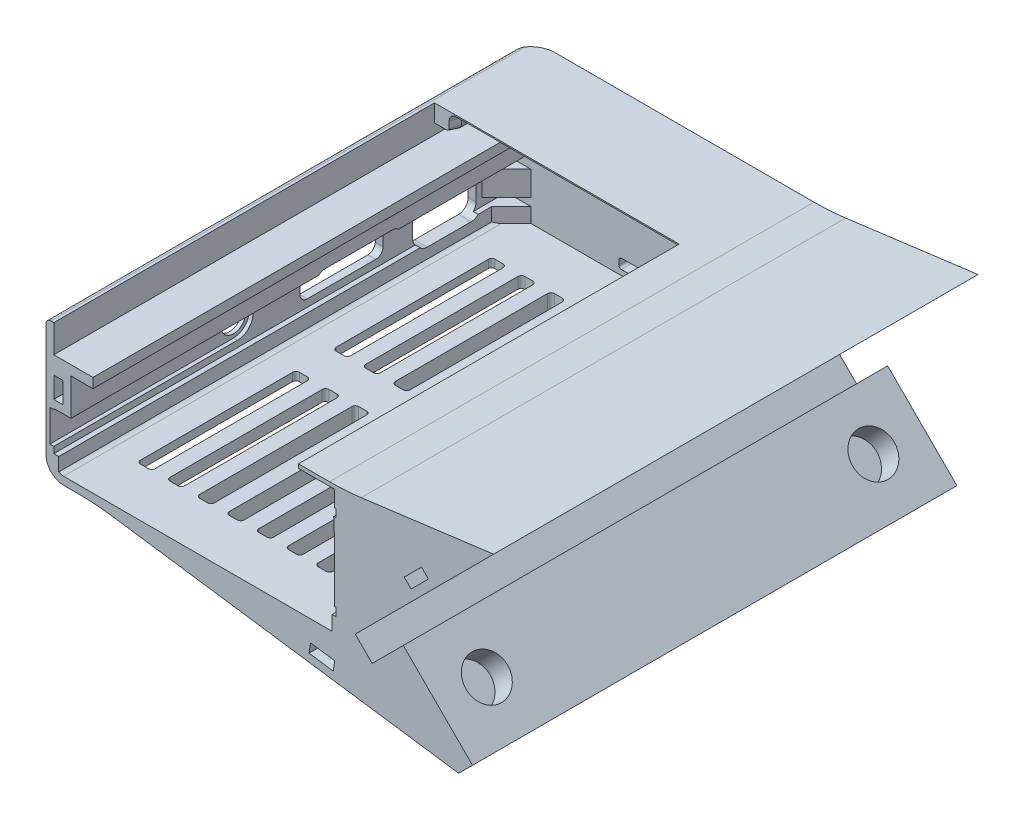
SolidWorks part; units mm, degrees
ref_plane "Front Plane" through (0, 0, 0) normal (0, 0, 1) x (1, 0, 0)
ref_plane "Top Plane" through (0, 0, 0) normal (0, 1, 0) x (1, 0, 0)
ref_plane "Right Plane" through (0, 0, 0) normal (1, 0, 0) x (0, 0, -1)
sketch "Sketch1" plane through (0, 0, 0) normal (0, 0, 1) x (1, 0, 0)
  line L0 (1.6, 5.9) -> (1.6, 3.6) construction
  line L1 (3.6, 0) -> (61.2, 0)
  line L2 (0, 3.6) -> (0, 26.8)
  line L3 (49.6, 27.8) -> (61.2, 27.8)
  line L4 (61.2, 0) -> (61.2, 27.8)
  line L5 (3.6, 1.6) -> (57, 1.6) construction
  line L6 (1.6, 5.9) -> (0.8, 5.9) construction
  line L7 (0.8, 5.9) -> (0.8, 12.4) construction
  line L8 (0.8, 12.4) -> (1.6, 12.4) construction
  line L9 (1.6, 12.4) -> (1.6, 22.1) construction
  line L10 (1.6, 5.9) -> (1.6, 12.4) construction
  line L11 (1, 27.8) -> (1.6, 27.8)
  line L12 (59, 3.6) -> (59, 22.1) construction
  line L13 (59, 4.6) -> (59.3, 4.6) construction
  line L14 (59.3, 4.6) -> (59.3, 6.1) construction
  line L15 (59.3, 6.1) -> (59, 6.1) construction
  line L16 (59, 22.1) -> (59.3, 22.1) construction
  line L17 (59.3, 22.1) -> (59.3, 23.6) construction
  line L18 (59.3, 23.6) -> (59, 23.6) construction
  line L19 (59, 23.6) -> (59, 27.2) construction
  line L20 (1.6, 22.1) -> (5.6, 22.1) construction
  line L21 (5.6, 22.1) -> (5.6, 23.6) construction
  line L22 (5.6, 23.6) -> (1.6, 23.6) construction
  line L23 (1.6, 23.6) -> (1.6, 27.8) construction
  line L24 (59, 27.2) -> (49.6, 27.2) construction
  line L25 (49.6, 27.2) -> (49.6, 27.8) construction
  line L26 (49.6, 27.8) -> (1.6, 27.8)
  arc A0 (3.6, 0) -> (0, 3.6) centre (3.6, 3.6) cw
  arc A1 (0, 26.8) -> (1, 27.8) centre (1, 26.8) cw
  arc A2 (1.6, 3.6) -> (3.6, 1.6) centre (3.6, 3.6) ccw construction
  arc A3 (57, 1.6) -> (59, 3.6) centre (57, 3.6) ccw construction
  point P7 (0, 0)
  dimension "D2" = 0.8
  dimension "D3" = 2
  dimension "D8" = 2
  dimension "D18" = 1
  dimension "D1" = 61.2
  dimension "D4" = 5.9
  dimension "D5" = 1.6
  dimension "D6" = 6.5
  dimension "D7" = 2.2
  dimension "D9" = 4.6
  dimension "D10" = 6.1
  dimension "D11" = 0.3
  dimension "D12" = 16
  dimension "D13" = 4
  dimension "D14" = 1.5
  dimension "D15" = 4.2
  dimension "D16" = 0.6
  dimension "D17" = 48
extrude "Boss-Extrude1" add sketch "Sketch1" along normal blind 94
sketch "Sketch2" plane through (0, 0, 94) normal (0, 0, 1) x (1, 0, 0)
  line L0 (51.6, 27.8) -> (51.6, 27)
  line L1 (59.3, 4.6) -> (59, 4.6)
  line L2 (51.6, 27) -> (59, 27)
  line L3 (1.6, 27.8) -> (1.6, 22.1)
  line L4 (1.6, 27.8) -> (1, 27.8) construction
  line L5 (61.2, 0) -> (61.2, 27.8)
  line L6 (61.2, 27.8) -> (1, 27.8)
  line L7 (0, 26.8) -> (0, 3.6)
  line L8 (3.6, 0) -> (61.2, 0)
  line L9 (61.2, 0) -> (61.2, 27.8) construction
  line L10 (61.2, 27.8) -> (51.6, 27.8) construction
  line L11 (0, 26.8) -> (0, 3.6) construction
  line L12 (3.6, 0) -> (61.2, 0) construction
  line L13 (1.6, 22.1) -> (9.6, 22.1)
  line L14 (9.6, 22.1) -> (9.6, 20.1)
  line L15 (9.6, 20.1) -> (5.1, 20.1)
  line L16 (59, 1.6) -> (3.6, 1.6)
  line L17 (1.6, 12.6) -> (1.6, 3.6)
  line L18 (1.6, 12.6) -> (5.1, 12.6)
  line L19 (5.1, 12.6) -> (5.1, 20.1)
  line L20 (59, 27) -> (59, 23.7)
  line L21 (59, 23.7) -> (59.3, 23.7)
  line L22 (59.3, 23.7) -> (59.3, 22.1)
  line L23 (59.3, 22.1) -> (59, 22.1)
  line L24 (59, 6.2) -> (59.3, 6.2)
  line L25 (59.3, 6.2) -> (59.3, 4.6)
  line L26 (59, 4.6) -> (59, 1.6)
  line L27 (59, 22.1) -> (59, 6.2)
  line L28 (1.6, 27.8) -> (51.6, 27.8)
  line L29 (51.6, 27.8) -> (51.599, 27.8897)
  arc A0 (1.6, 3.6) -> (3.6, 1.6) centre (3.6, 3.6) ccw
  arc A2 (1, 27.8) -> (0, 26.8) centre (1, 26.8) ccw
  arc A3 (0, 3.6) -> (3.6, 0) centre (3.6, 3.6) ccw
  arc A4 (1, 27.8) -> (0, 26.8) centre (1, 26.8) ccw construction
  arc A5 (0, 3.6) -> (3.6, 0) centre (3.6, 3.6) ccw construction
  line M8 (61.2, 27.8) -> (1, 27.8)
  dimension "D7" = 2
  dimension "D2" = 50
  dimension "D3" = 1.6
  dimension "D4" = 5.7
  dimension "D5" = 8
  dimension "D6" = 1.6
  dimension "D8" = 11
  dimension "D9" = 2
  dimension "D10" = 5.1
  dimension "D11" = 2.2
  dimension "D12" = 0.8
  dimension "D13" = 3.3
  dimension "D14" = 0.3
  dimension "D15" = 1.6
  dimension "D16" = 1.6
  dimension "D17" = 3
  dimension "D1" = 0
extrude "Cut-Extrude1" cut sketch "Sketch2" against normal offset from surface (92.5 mm away) 1.5 contours L17 A0 L16 L26 L1 L25 L24 L27 L23 L22 L21 L20 L2 L0 L3 L13 L14 L15 L19 L18 M8 region at (30.9914, 14.5554, 94) up to face at (21.0079, 14.2436, 0)
chamfer "Chamfer1" distance 5 angle 45 1 edges at (59, 3.1, 1.5)
sketch "Sketch3" plane through (0, 0, 1.5) normal (0, 0, 1) x (1, 0, 0)
  line L0 (1.6, 27.8) -> (1.6, 22.1) construction
  line L1 (51.6, 27.8) -> (1.6, 27.8)
  line L2 (51.6, 27.8) -> (51.6, 27)
  line L3 (51.6, 27) -> (6.1, 27)
  line L4 (1.6, 27.8) -> (1.6, 23.7)
  line L5 (51.6, 27) -> (59, 27) construction
  line L6 (5.1, 26) -> (5.1, 24.7)
  line L7 (4.1, 23.7) -> (1.6, 23.7)
  line L8 (59, 23.7) -> (59.3, 23.7) construction
  line L9 (5.1, 12.6) -> (5.1, 20.1) construction
  arc A0 (5.1, 26) -> (6.1, 27) centre (6.1, 26) cw
  arc A1 (5.1, 24.7) -> (4.1, 23.7) centre (4.1, 24.7) cw
  dimension "D1" = 1
extrude "Boss-Extrude2" add sketch "Sketch3" along normal blind 14.7
sketch "Sketch4" plane through (0, 4.6, 0) normal (0, 1, 0) x (1, 0, 0)
  line L0 (1.6, -1.5) -> (6.6, -1.5)
  line L1 (54, -1.5) -> (3.6, -1.5) construction
  line L2 (6.6, -1.5) -> (1.6, -6.5)
  line L3 (1.6, -1.5) -> (1.6, -94) construction
  line L4 (1.6, -6.5) -> (1.6, -1.5)
  dimension "D1" = 45
extrude "Boss-Extrude3" add sketch "Sketch4" against normal up to next
sketch "Sketch5" plane through (0, 6.2, 0) normal (0, -1, 0) x (1, 0, 0)
  line L0 (54, 1.5) -> (59, 6.5)
  line L1 (59, 6.5) -> (59, 1.5)
  line L2 (59, 1.5) -> (59, 94) construction
  line L3 (59, 1.5) -> (59.3, 1.5) construction
  line L4 (59, 1.5) -> (54, 1.5)
  line L5 (1.6, 1.5) -> (6.6, 1.5)
  line L6 (6.6, 1.5) -> (1.6, 6.5)
  line L7 (1.6, 6.5) -> (1.6, 1.5)
extrude "Boss-Extrude4" add sketch "Sketch5" against normal blind 5
sketch "Sketch18" plane through (0, 0, 94) normal (0, 0, 1) x (1, 0, 0)
  line L0 (59, 1.6) -> (54, 1.6) construction
  line L1 (59, 4.6) -> (58.5, 4.6)
  line L2 (59, 4.6) -> (59, 1.6)
  line L3 (59, 1.6) -> (58.5, 1.6)
  line L4 (58.5, 4.6) -> (58.5, 1.6)
  line L5 (59, 1.6) -> (3.6, 1.6) construction
  line L6 (1.6, 4.6) -> (2.6, 4.6)
  line L7 (1.6, 4.6) -> (1.6, 1.6)
  line L8 (1.6, 1.6) -> (2.6, 1.6)
  line L9 (2.6, 4.6) -> (2.6, 1.6)
  line L10 (59, 22.1) -> (58.8, 22.1)
  line L11 (58.8, 22.1) -> (59, 17.1)
  line L12 (59, 22.1) -> (59, 11.2) construction
  line L13 (59, 17.1) -> (59, 22.1)
  dimension "D1" = 1
  dimension "D2" = 0.5
  dimension "D3" = 0.2
  dimension "D4" = 5
sketch "Sketch6" plane through (0, 0, 0) normal (-1, 0, 0) x (0, 0, 1)
  line L0 (0, 26.8) -> (0, 3.6) construction
  line L1 (9.7, 12) -> (18.7, 12)
  line L2 (7.7, 10) -> (7.7, 6)
  line L3 (9.7, 4) -> (18.7, 4)
  line L4 (20.7, 10) -> (20.7, 6)
  line L5 (28.2, 13.1) -> (42.2, 13.1)
  line L6 (26.7, 11.6) -> (26.7, 7.6)
  line L7 (28.2, 6.1) -> (42.2, 6.1)
  line L8 (43.7, 11.6) -> (43.7, 7.6)
  line L9 (94, 0) -> (0, 0) construction
  arc A0 (7.7, 6) -> (9.7, 4) centre (9.7, 6) ccw
  arc A1 (18.7, 4) -> (20.7, 6) centre (18.7, 6) ccw
  arc A2 (18.7, 12) -> (20.7, 10) centre (18.7, 10) cw
  arc A3 (9.7, 12) -> (7.7, 10) centre (9.7, 10) ccw
  arc A4 (26.7, 7.6) -> (28.2, 6.1) centre (28.2, 7.6) ccw
  arc A5 (42.2, 6.1) -> (43.7, 7.6) centre (42.2, 7.6) ccw
  arc A6 (42.2, 13.1) -> (43.7, 11.6) centre (42.2, 11.6) cw
  arc A7 (28.2, 13.1) -> (26.7, 11.6) centre (28.2, 11.6) ccw
  circle A8 centre (56.5, 9.15) radius 2.5
  point P12 (7.7, 4)
  point P15 (20.7, 4)
  point P20 (7.7, 12)
  point P25 (26.7, 6.1)
  point P30 (43.7, 13.1)
  point P33 (26.7, 13.1)
  dimension "D4" = 2
  dimension "D10" = 1.5
  dimension "D11" = 5
  dimension "D12" = 9.15
  dimension "D13" = 48.8
  dimension "D1" = 7.7
  dimension "D2" = 13
  dimension "D3" = 8
  dimension "D5" = 4
  dimension "D6" = 19
  dimension "D7" = 2.1
  dimension "D8" = 7
  dimension "D9" = 17
extrude "Boss-Extrude9" add sketch "Sketch18" against normal up to next
extrude "Cut-Extrude2" cut sketch "Sketch6" against normal up to next
sketch "Sketch7" plane through (1.6, 0, 0) normal (1, 0, 0) x (0, 0, -1)
  line L0 (-56.5, 5.9) -> (-94, 5.9)
  line L1 (-94, 12.6) -> (-94, 4.6) construction
  line L2 (-94, 5.9) -> (-94, 12.4)
  line L3 (-94, 12.4) -> (-56.5, 12.4)
  line L4 (-4.5, 1.6) -> (-94, 1.6) construction
  arc A0 (-56.5, 5.9) -> (-56.5, 12.4) centre (-56.5, 9.15) ccw
  dimension "D1" = 4.3
extrude "Cut-Extrude3" cut sketch "Sketch7" against normal blind 0.8
sketch "Sketch8" plane through (0, 0, 1.5) normal (0, 0, 1) x (1, 0, 0)
  line L0 (59, 17.1) -> (59, 6.2) construction
  line L1 (25.1, 4.7) -> (37.9, 4.7)
  line L2 (24.6, 4.2) -> (24.6, 3.2)
  line L3 (25.1, 2.7) -> (37.9, 2.7)
  line L4 (38.4, 4.2) -> (38.4, 3.2)
  line L5 (58.5, 1.6) -> (3.6, 1.6) construction
  arc A0 (37.9, 4.7) -> (38.4, 4.2) centre (37.9, 4.2) cw
  arc A1 (37.9, 2.7) -> (38.4, 3.2) centre (37.9, 3.2) ccw
  arc A2 (24.6, 3.2) -> (25.1, 2.7) centre (25.1, 3.2) ccw
  arc A3 (25.1, 4.7) -> (24.6, 4.2) centre (25.1, 4.2) ccw
  point P10 (38.4, 4.7)
  point P15 (24.6, 2.7)
  point P18 (24.6, 4.7)
  dimension "D5" = 0.5
  dimension "D1" = 13.8
  dimension "D2" = 20.6
  dimension "D3" = 1.1
  dimension "D4" = 2
extrude "Cut-Extrude4" cut sketch "Sketch8" against normal through all
sketch "Sketch9" plane through (0, 27.8, 0) normal (0, 1, 0) x (1, 0, 0)
  line L0 (61.2, -94) -> (61.2, 0) construction
  line L1 (0, 0) -> (61.2, 0)
  line L3 (5, 5) -> (61.2, 5)
  line L4 (61.2, 0) -> (61.2, 5)
  arc A0 (0, 0) -> (5, 5) centre (5, 0) cw
  dimension "D1" = 5
extrude "Boss-Extrude5" add sketch "Sketch9" against normal up to surface (27.8 mm away) up to face at (32.4, 0, 47)
sketch "Sketch10" plane through (0, 0, 94) normal (0, 0, 1) x (1, 0, 0)
  line L2 (1, 27.8) -> (0, 27.8)
  line L3 (0, 27.8) -> (0, 26.8)
  line L4 (1, 27.8) -> (0, 27.8)
  line L6 (0, 27.8) -> (0, 26.8)
  line L8 (0, 3.6) -> (0, 0)
  line L9 (0, 0) -> (3.6, 0)
  line L10 (0, 3.6) -> (0, 0)
  line L11 (0, 0) -> (3.6, 0)
  line L14 (38.4, 3.2) -> (38.4, 4.2)
  line L15 (37.9, 4.7) -> (25.1, 4.7)
  line L16 (24.6, 4.2) -> (24.6, 3.2)
  line L17 (25.1, 2.7) -> (37.9, 2.7)
  line L18 (38.4, 3.2) -> (38.4, 4.2)
  line L19 (37.9, 4.7) -> (25.1, 4.7)
  line L20 (24.6, 4.2) -> (24.6, 3.2)
  line L21 (25.1, 2.7) -> (37.9, 2.7)
  arc A3 (1, 27.8) -> (0, 26.8) centre (1, 26.8) ccw
  arc A4 (1, 27.8) -> (0, 26.8) centre (1, 26.8) ccw
  arc A5 (0, 3.6) -> (3.6, 0) centre (3.6, 3.6) ccw
  arc A6 (0, 3.6) -> (3.6, 0) centre (3.6, 3.6) ccw
  arc A10 (38.4, 4.2) -> (37.9, 4.7) centre (37.9, 4.2) ccw
  arc A11 (25.1, 4.7) -> (24.6, 4.2) centre (25.1, 4.2) ccw
  arc A12 (24.6, 3.2) -> (25.1, 2.7) centre (25.1, 3.2) ccw
  arc A13 (37.9, 2.7) -> (38.4, 3.2) centre (37.9, 3.2) ccw
  arc A14 (38.4, 4.2) -> (37.9, 4.7) centre (37.9, 4.2) ccw
  arc A15 (25.1, 4.7) -> (24.6, 4.2) centre (25.1, 4.2) ccw
  arc A16 (24.6, 3.2) -> (25.1, 2.7) centre (25.1, 3.2) ccw
  arc A17 (37.9, 2.7) -> (38.4, 3.2) centre (37.9, 3.2) ccw
  dimension "D1" = 0
  dimension "D2" = 0
  dimension "D3" = 0
extrude "Cut-Extrude5" cut sketch "Sketch10" against normal through all
sketch "Sketch11" plane through (0, 0, 0) normal (0, 0, 1) x (1, 0, 0)
  line L0 (61.2, 27.8) -> (91.4843, 31.7491)
  line L1 (3.6, 0) -> (61.2, 0) construction
  line L2 (0, 26.8) -> (0, 3.6) construction
  line L3 (91.4843, 31.7491) -> (63.2, 3.4648)
  line L4 (63.2, 3.4648) -> (66.6648, 0)
  line L5 (66.6648, 0) -> (73.0288, 6.364)
  line L6 (73.0288, 6.364) -> (87.1709, -7.7782)
  line L7 (61.2, 27.8) -> (61.2, 0)
  line L8 (61.2, 0) -> (10, 0)
  line L9 (10, 0) -> (84.3425, -10.6066)
  line L10 (84.3425, -10.6066) -> (87.1709, -7.7782)
  dimension "D1" = 2
  dimension "D2" = 40
  dimension "D3" = 4.9
  dimension "D4" = 9
  dimension "D5" = 20
  dimension "D6" = 45
  dimension "D7" = 4
  dimension "D8" = 10
extrude "Boss-Extrude6" add sketch "Sketch11" along normal up to surface (94 mm away) and the other way up to surface (5 mm away) up to face at (27.2832, 14.2872, 94) other way up to face at (31.5, 3.7, -5)
fillet "Fillet1" radius 50 1 edges at (10, 0, 44.5)
fillet "Fillet2" radius 50 1 edges at (61.2, 27.8, 44.5)
sketch "Sketch12" plane through (0, 0, 94) normal (0, 0, 1) x (1, 0, 0)
  line L0 (0, 26.8) -> (0, 3.6) construction
  line L1 (1.6, 18.5) -> (3.5, 18.5)
  line L2 (1.6, 18.5) -> (1.6, 14.2)
  line L3 (1.6, 14.2) -> (3.5, 14.2)
  line L4 (3.5, 18.5) -> (3.5, 14.2)
  line L5 (1.6, 12.6) -> (5.1, 12.6) construction
  line L6 (5.1, 12.6) -> (5.1, 20.1) construction
  line L7 (9.6, 20.1) -> (5.1, 20.1) construction
  line L8 (54.0501, -2.6483) -> (53.7676, -4.6282)
  line L9 (54.0501, -2.6483) -> (59, -3.3545)
  line L10 (53.7676, -4.6282) -> (58.7175, -5.3344)
  line L11 (59, -3.3545) -> (58.7175, -5.3344)
  line L12 (59, 17.1) -> (59, 6.2) construction
  line L13 (84.3425, -10.6066) -> (13.5133, -0.5012) construction
  line L15 (73.2085, 18.5645) -> (74.6227, 17.1503)
  line L16 (73.2085, 18.5645) -> (76.744, 22.1)
  line L17 (74.6227, 17.1503) -> (78.1582, 20.6858)
  line L18 (76.744, 22.1) -> (78.1582, 20.6858)
  line L19 (91.4843, 31.7491) -> (63.2, 3.4648) construction
  line L20 (59.3, 22.1) -> (58.8, 22.1) construction
  dimension "D1" = 1.6
  dimension "D2" = 1.6
  dimension "D3" = 1.6
  dimension "D4" = 1.6
  dimension "D5" = 1.6
  dimension "D6" = 2
  dimension "D7" = 5
  dimension "D8" = 1.6
  dimension "D9" = 5
  dimension "D10" = 2
extrude "Cut-Extrude6" cut sketch "Sketch12" against normal blind 10
sketch "Sketch13" plane through (39.6964, 39.6964, 0) normal (0.7071, 0.7071, 0) x (0, 0, -1)
  line L0 (5, -57.1391) -> (-49995, -57.1391) construction
  line L1 (5, -67.1391) -> (5, -47.1391) construction
  line L2 (-94, -47.1391) -> (-94, -67.1391) construction
  circle A0 centre (-84, -57.1391) radius 4.25
  circle A1 centre (-5, -57.1391) radius 4.25
  point P4 (5, -57.1391)
  dimension "D1" = 10
  dimension "D2" = 8.5
  dimension "D3" = 10
  dimension "D4" = 8.5
extrude "Cut-Extrude7" cut sketch "Sketch13" against normal blind 5
sketch "Sketch14" plane through (47.4745, -47.4745, 0) normal (0.7071, -0.7071, 0) x (0, 0, -1)
  line L0 (-94, 56.1391) -> (-94, 52.1391) construction
  line L1 (-74, 54.1391) -> (-49, 54.1391)
  line L2 (-74, 54.1391) -> (-74, 52.1391)
  line L3 (-74, 52.1391) -> (-49, 52.1391)
  line L4 (-49, 54.1391) -> (-49, 52.1391)
  line L5 (-94, 56.1391) -> (5, 56.1391) construction
  dimension "D1" = 25
  dimension "D2" = 20
  dimension "D3" = 2
  dimension "D4" = 2
extrude "Cut-Extrude8" cut sketch "Sketch14" against normal up to surface (37.8397 mm away) up to face at (59, 11.5, 34)
sketch "Sketch16" plane through (0, 1.6, 0) normal (0, 1, 0) x (1, 0, 0)
  line L1 (54, -1.5) -> (6.6, -1.5) construction
  line L2 (9.3, -11.5) -> (10.9, -11.5)
  line L3 (8.6, -12.2) -> (8.6, -43.3)
  line L4 (9.3, -44) -> (10.9, -44)
  line L5 (59, -6.5) -> (59, -94) construction
  line L8 (11.6, -12.2) -> (11.6, -43.3)
  line L9 (3.6, -4.5) -> (3.6, -94) construction
  line L10 (15.3571, -11.5) -> (16.9571, -11.5)
  line L11 (14.6571, -12.2) -> (14.6571, -43.3)
  line L12 (15.3571, -44) -> (16.9571, -44)
  line L13 (17.6571, -12.2) -> (17.6571, -43.3)
  line L14 (21.4143, -11.5) -> (23.0143, -11.5)
  line L15 (20.7143, -12.2) -> (20.7143, -43.3)
  line L16 (21.4143, -44) -> (23.0143, -44)
  line L17 (23.7143, -12.2) -> (23.7143, -43.3)
  line L18 (27.4714, -11.5) -> (29.0714, -11.5)
  line L19 (26.7714, -12.2) -> (26.7714, -43.3)
  line L20 (27.4714, -44) -> (29.0714, -44)
  line L21 (29.7714, -12.2) -> (29.7714, -43.3)
  line L22 (33.5286, -11.5) -> (35.1286, -11.5)
  line L23 (32.8286, -12.2) -> (32.8286, -43.3)
  line L24 (33.5286, -44) -> (35.1286, -44)
  line L25 (35.8286, -12.2) -> (35.8286, -43.3)
  line L26 (39.5857, -11.5) -> (41.1857, -11.5)
  line L27 (38.8857, -12.2) -> (38.8857, -43.3)
  line L28 (39.5857, -44) -> (41.1857, -44)
  line L29 (41.8857, -12.2) -> (41.8857, -43.3)
  line L30 (45.6429, -11.5) -> (47.2429, -11.5)
  line L31 (44.9429, -12.2) -> (44.9429, -43.3)
  line L32 (45.6429, -44) -> (47.2429, -44)
  line L33 (47.9429, -12.2) -> (47.9429, -43.3)
  line L34 (51.7, -11.5) -> (53.3, -11.5)
  line L35 (51, -12.2) -> (51, -43.3)
  line L36 (51.7, -44) -> (53.3, -44)
  line L37 (54, -12.2) -> (54, -43.3)
  line L38 (15.3571, -51.5) -> (16.9571, -51.5)
  line L39 (14.6571, -52.2) -> (14.6571, -83.3)
  line L40 (15.3571, -84) -> (16.9571, -84)
  line L41 (17.6571, -52.2) -> (17.6571, -83.3)
  line L42 (21.4143, -51.5) -> (23.0143, -51.5)
  line L43 (20.7143, -52.2) -> (20.7143, -83.3)
  line L44 (21.4143, -84) -> (23.0143, -84)
  line L45 (23.7143, -52.2) -> (23.7143, -83.3)
  line L46 (27.4714, -51.5) -> (29.0714, -51.5)
  line L47 (26.7714, -52.2) -> (26.7714, -83.3)
  line L48 (27.4714, -84) -> (29.0714, -84)
  line L49 (29.7714, -52.2) -> (29.7714, -83.3)
  line L50 (33.5286, -51.5) -> (35.1286, -51.5)
  line L51 (32.8286, -52.2) -> (32.8286, -83.3)
  line L52 (33.5286, -84) -> (35.1286, -84)
  line L53 (35.8286, -52.2) -> (35.8286, -83.3)
  line L54 (39.5857, -51.5) -> (41.1857, -51.5)
  line L55 (38.8857, -52.2) -> (38.8857, -83.3)
  line L56 (39.5857, -84) -> (41.1857, -84)
  line L57 (41.8857, -52.2) -> (41.8857, -83.3)
  line L58 (45.6429, -51.5) -> (47.2429, -51.5)
  line L59 (44.9429, -52.2) -> (44.9429, -83.3)
  line L60 (45.6429, -84) -> (47.2429, -84)
  line L61 (47.9429, -52.2) -> (47.9429, -83.3)
  line L62 (51.7, -51.5) -> (53.3, -51.5)
  line L63 (51, -52.2) -> (51, -83.3)
  line L64 (51.7, -84) -> (53.3, -84)
  line L65 (54, -52.2) -> (54, -83.3)
  line L66 (9.3, -51.5) -> (10.9, -51.5)
  line L67 (8.6, -52.2) -> (8.6, -83.3)
  line L68 (9.3, -84) -> (10.9, -84)
  line L69 (11.6, -52.2) -> (11.6, -83.3)
  line L70 (58.5, -94) -> (3.6, -94) construction
  arc A0 (10.9, -44) -> (11.6, -43.3) centre (10.9, -43.3) ccw
  arc A1 (8.6, -43.3) -> (9.3, -44) centre (9.3, -43.3) ccw
  arc A2 (10.9, -11.5) -> (11.6, -12.2) centre (10.9, -12.2) cw
  arc A3 (9.3, -11.5) -> (8.6, -12.2) centre (9.3, -12.2) ccw
  arc A4 (16.9571, -44) -> (17.6571, -43.3) centre (16.9571, -43.3) ccw
  arc A5 (14.6571, -43.3) -> (15.3571, -44) centre (15.3571, -43.3) ccw
  arc A6 (16.9571, -11.5) -> (17.6571, -12.2) centre (16.9571, -12.2) cw
  arc A7 (15.3571, -11.5) -> (14.6571, -12.2) centre (15.3571, -12.2) ccw
  arc A8 (23.0143, -44) -> (23.7143, -43.3) centre (23.0143, -43.3) ccw
  arc A9 (20.7143, -43.3) -> (21.4143, -44) centre (21.4143, -43.3) ccw
  arc A10 (23.0143, -11.5) -> (23.7143, -12.2) centre (23.0143, -12.2) cw
  arc A11 (21.4143, -11.5) -> (20.7143, -12.2) centre (21.4143, -12.2) ccw
  arc A12 (29.0714, -44) -> (29.7714, -43.3) centre (29.0714, -43.3) ccw
  arc A13 (26.7714, -43.3) -> (27.4714, -44) centre (27.4714, -43.3) ccw
  arc A14 (29.0714, -11.5) -> (29.7714, -12.2) centre (29.0714, -12.2) cw
  arc A15 (27.4714, -11.5) -> (26.7714, -12.2) centre (27.4714, -12.2) ccw
  arc A16 (35.1286, -44) -> (35.8286, -43.3) centre (35.1286, -43.3) ccw
  arc A17 (32.8286, -43.3) -> (33.5286, -44) centre (33.5286, -43.3) ccw
  arc A18 (35.1286, -11.5) -> (35.8286, -12.2) centre (35.1286, -12.2) cw
  arc A19 (33.5286, -11.5) -> (32.8286, -12.2) centre (33.5286, -12.2) ccw
  arc A20 (41.1857, -44) -> (41.8857, -43.3) centre (41.1857, -43.3) ccw
  arc A21 (38.8857, -43.3) -> (39.5857, -44) centre (39.5857, -43.3) ccw
  arc A22 (41.1857, -11.5) -> (41.8857, -12.2) centre (41.1857, -12.2) cw
  arc A23 (39.5857, -11.5) -> (38.8857, -12.2) centre (39.5857, -12.2) ccw
  arc A24 (47.2429, -44) -> (47.9429, -43.3) centre (47.2429, -43.3) ccw
  arc A25 (44.9429, -43.3) -> (45.6429, -44) centre (45.6429, -43.3) ccw
  arc A26 (47.2429, -11.5) -> (47.9429, -12.2) centre (47.2429, -12.2) cw
  arc A27 (45.6429, -11.5) -> (44.9429, -12.2) centre (45.6429, -12.2) ccw
  arc A28 (53.3, -44) -> (54, -43.3) centre (53.3, -43.3) ccw
  arc A29 (51, -43.3) -> (51.7, -44) centre (51.7, -43.3) ccw
  arc A30 (53.3, -11.5) -> (54, -12.2) centre (53.3, -12.2) cw
  arc A31 (51.7, -11.5) -> (51, -12.2) centre (51.7, -12.2) ccw
  arc A32 (16.9571, -84) -> (17.6571, -83.3) centre (16.9571, -83.3) ccw
  arc A33 (14.6571, -83.3) -> (15.3571, -84) centre (15.3571, -83.3) ccw
  arc A34 (16.9571, -51.5) -> (17.6571, -52.2) centre (16.9571, -52.2) cw
  arc A35 (15.3571, -51.5) -> (14.6571, -52.2) centre (15.3571, -52.2) ccw
  arc A36 (23.0143, -84) -> (23.7143, -83.3) centre (23.0143, -83.3) ccw
  arc A37 (20.7143, -83.3) -> (21.4143, -84) centre (21.4143, -83.3) ccw
  arc A38 (23.0143, -51.5) -> (23.7143, -52.2) centre (23.0143, -52.2) cw
  arc A39 (21.4143, -51.5) -> (20.7143, -52.2) centre (21.4143, -52.2) ccw
  arc A40 (29.0714, -84) -> (29.7714, -83.3) centre (29.0714, -83.3) ccw
  arc A41 (26.7714, -83.3) -> (27.4714, -84) centre (27.4714, -83.3) ccw
  arc A42 (29.0714, -51.5) -> (29.7714, -52.2) centre (29.0714, -52.2) cw
  arc A43 (27.4714, -51.5) -> (26.7714, -52.2) centre (27.4714, -52.2) ccw
  arc A44 (35.1286, -84) -> (35.8286, -83.3) centre (35.1286, -83.3) ccw
  arc A45 (32.8286, -83.3) -> (33.5286, -84) centre (33.5286, -83.3) ccw
  arc A46 (35.1286, -51.5) -> (35.8286, -52.2) centre (35.1286, -52.2) cw
  arc A47 (33.5286, -51.5) -> (32.8286, -52.2) centre (33.5286, -52.2) ccw
  arc A48 (41.1857, -84) -> (41.8857, -83.3) centre (41.1857, -83.3) ccw
  arc A49 (38.8857, -83.3) -> (39.5857, -84) centre (39.5857, -83.3) ccw
  arc A50 (41.1857, -51.5) -> (41.8857, -52.2) centre (41.1857, -52.2) cw
  arc A51 (39.5857, -51.5) -> (38.8857, -52.2) centre (39.5857, -52.2) ccw
  arc A52 (47.2429, -84) -> (47.9429, -83.3) centre (47.2429, -83.3) ccw
  arc A53 (44.9429, -83.3) -> (45.6429, -84) centre (45.6429, -83.3) ccw
  arc A54 (47.2429, -51.5) -> (47.9429, -52.2) centre (47.2429, -52.2) cw
  arc A55 (45.6429, -51.5) -> (44.9429, -52.2) centre (45.6429, -52.2) ccw
  arc A56 (53.3, -84) -> (54, -83.3) centre (53.3, -83.3) ccw
  arc A57 (51, -83.3) -> (51.7, -84) centre (51.7, -83.3) ccw
  arc A58 (53.3, -51.5) -> (54, -52.2) centre (53.3, -52.2) cw
  arc A59 (51.7, -51.5) -> (51, -52.2) centre (51.7, -52.2) ccw
  arc A60 (10.9, -84) -> (11.6, -83.3) centre (10.9, -83.3) ccw
  arc A61 (8.6, -83.3) -> (9.3, -84) centre (9.3, -83.3) ccw
  arc A62 (10.9, -51.5) -> (11.6, -52.2) centre (10.9, -52.2) cw
  arc A63 (9.3, -51.5) -> (8.6, -52.2) centre (9.3, -52.2) ccw
  dimension "D3" = 0.7
  dimension "D1" = 3
  dimension "D2" = 32.5
  dimension "D4" = 10
  dimension "D5" = 5
  dimension "D8" = 10
  dimension "D9" = 5
  dimension "D6" = 8
  dimension "D7" = 2
extrude "Cut-Extrude9" cut sketch "Sketch16" against normal through all
chamfer "Chamfer2" distance 2 angle 15 5 edges at (28.85, 27, 16.2) (5.3929, 26.7071, 16.2) (5.1, 25.35, 16.2) (4.8071, 23.9929, 16.2) (2.85, 23.7, 16.2) first distance on face at (38.9, 27, 37.2333) first distance on face at (5.4964, 26.6036, 8.85) first distance on face at (5.1, 25.35, 8.85) first distance on face at (4.7036, 24.0964, 8.85) first distance on face at (2.85, 23.7, 8.85)
